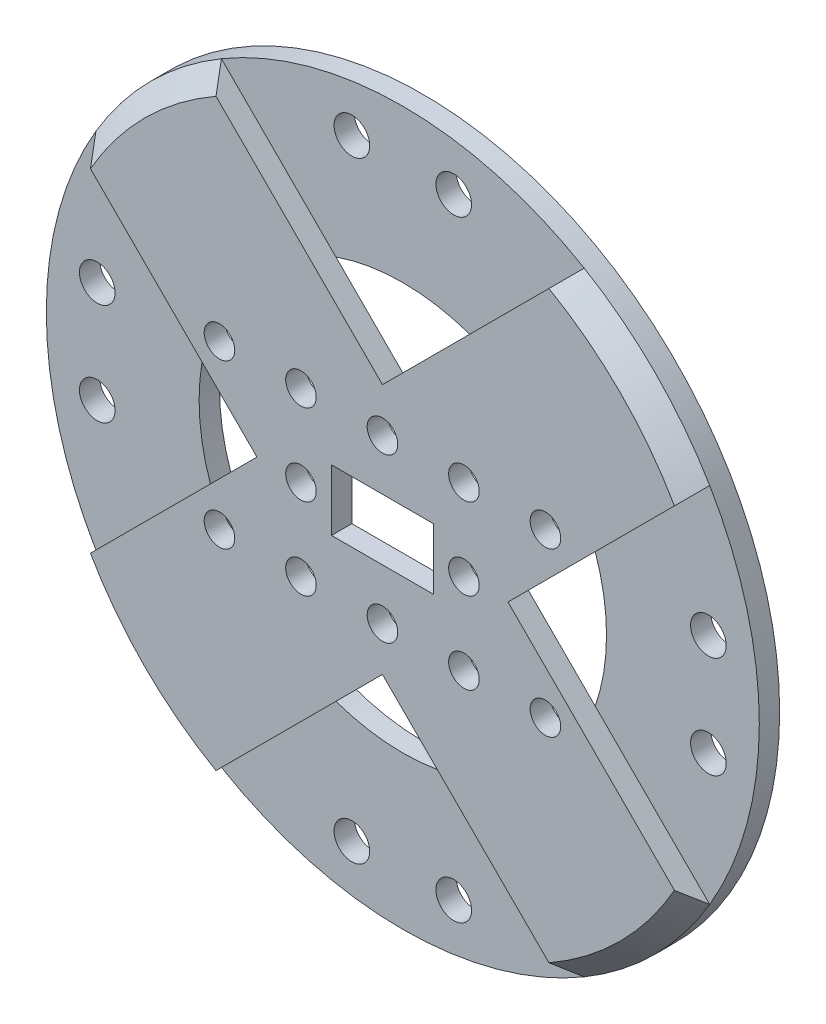
SolidWorks part; units mm, degrees
ref_plane "Front Plane" through (0, 0, 0) normal (0, 0, 1) x (1, 0, 0)
ref_plane "Top Plane" through (0, 0, 0) normal (0, 1, 0) x (1, 0, 0)
ref_plane "Right Plane" through (0, 0, 0) normal (1, 0, 0) x (0, 0, -1)
sketch "Sketch1" plane through (0, 0, 0) normal (0, 0, 1) x (1, 0, 0)
  circle A0 centre (0, 0) radius 35
  circle A1 centre (0, 0) radius 20
  dimension "D1" = 70
extrude "Boss-Extrude1" add sketch "Sketch1" along normal blind 2
sketch "Sketch2" plane through (0, 0, 2) normal (0, 0, 1) x (1, 0, 0)
  line L0 (0, 0) -> (0, 30) construction
  line L1 (-5, 30) -> (5, 30) construction
  circle A0 centre (5, 30) radius 1.75
  circle A1 centre (-5, 30) radius 1.75
  point P5 (0, 30)
  dimension "D3" = 3.5
  dimension "D4" = 3.5
  dimension "D1" = 30
  dimension "D2" = 10
extrude "Cut-Extrude1" cut sketch "Sketch2" against normal through all
pattern_circular "CirPattern1" count 4 every 90 about axis through (0, 0, 2) along (0, 0, 1) of "Cut-Extrude1"
sketch "Sketch3" plane through (0, 0, 2) normal (0, 0, 1) x (1, 0, 0)
  line L0 (-30.1306, -17.8085) -> (17.8085, 30.1306)
  line L3 (-17.8085, -30.1306) -> (30.1306, 17.8085)
  line L4 (-30.1306, -17.8085) -> (30.1306, 17.8085) construction
  line L5 (17.8085, 30.1306) -> (-17.8085, -30.1306) construction
  line L6 (0, 0) -> (0, 20) construction
  circle A0 centre (0, 0) radius 35 construction
  circle A1 centre (0, 0) radius 20 construction
  arc A2 (17.8085, 30.1306) -> (30.1306, 17.8085) centre (0, 0) cw
  arc A3 (-30.1306, -17.8085) -> (-17.8085, -30.1306) centre (0, 0) ccw
  point P1 (0, 0)
  point P16 (17.819, 30.1245)
  dimension "D1" = 45
extrude "Boss-Extrude2" add sketch "Sketch3" along normal blind 2
chamfer "Chamfer1" distance 2 angle 45 2 edges at (-24.7487, -24.7487, 4) (24.7487, 24.7487, 4)
pattern_circular "CirPattern2" count 2 every 90 of "Chamfer1", "Boss-Extrude2"
sketch "Sketch5" plane through (0, 0, 4) normal (0, 0, 1) x (1, 0, 0)
  line L0 (-8, 0) -> (8, 0) construction
  line L1 (-5, 3) -> (5, 3)
  line L2 (-5, 3) -> (-5, -3)
  line L3 (-5, -3) -> (5, -3)
  line L4 (5, 3) -> (5, -3)
  line L5 (-5, 3) -> (5, -3) construction
  line L6 (-5, -3) -> (5, 3) construction
  line L7 (0, 8) -> (0, -8) construction
  line L8 (-8, 8) -> (8, 8) construction
  line L9 (-8, -8) -> (8, -8) construction
  line L10 (-8, 8) -> (-16, 8) construction
  line L11 (-16, 8) -> (-16, -8) construction
  line L12 (-16, -8) -> (-8, -8) construction
  line L13 (8, -8) -> (16, -8) construction
  line L14 (16, -8) -> (16, 8) construction
  line L15 (16, 8) -> (8, 8) construction
  circle A0 centre (0, 8) radius 1.5
  circle A1 centre (-8, 8) radius 1.5
  circle A2 centre (-8, 0) radius 1.5
  circle A3 centre (-8, -8) radius 1.5
  circle A4 centre (8, -8) radius 1.5
  circle A5 centre (8, 0) radius 1.5
  circle A6 centre (8, 8) radius 1.5
  circle A7 centre (0, -8) radius 1.5
  circle A8 centre (-16, 8) radius 1.5
  circle A9 centre (-16, 0) radius 1.5
  circle A10 centre (-16, -8) radius 1.5
  circle A11 centre (16, -8) radius 1.5
  circle A12 centre (16, 0) radius 1.5
  circle A13 centre (16, 8) radius 1.5
  point P0 (0, 0)
  point P9 (0, 0)
  point P10 (0, 0)
  point P25 (0, 8)
  point P36 (0, 0)
  dimension "D5" = 3
  dimension "D6" = 3
  dimension "D7" = 3
  dimension "D8" = 3
  dimension "D9" = 3
  dimension "D10" = 3
  dimension "D11" = 3
  dimension "D12" = 3
  dimension "D17" = 3
  dimension "D18" = 3
  dimension "D19" = 3
  dimension "D20" = 3
  dimension "D21" = 3
  dimension "D22" = 3
  dimension "D1" = 10
  dimension "D2" = 6
  dimension "D3" = 16
  dimension "D4" = 16
  dimension "D13" = 16
  dimension "D14" = 16
  dimension "D15" = 8
  dimension "D16" = 8
extrude "Cut-Extrude2" cut sketch "Sketch5" against normal through all
